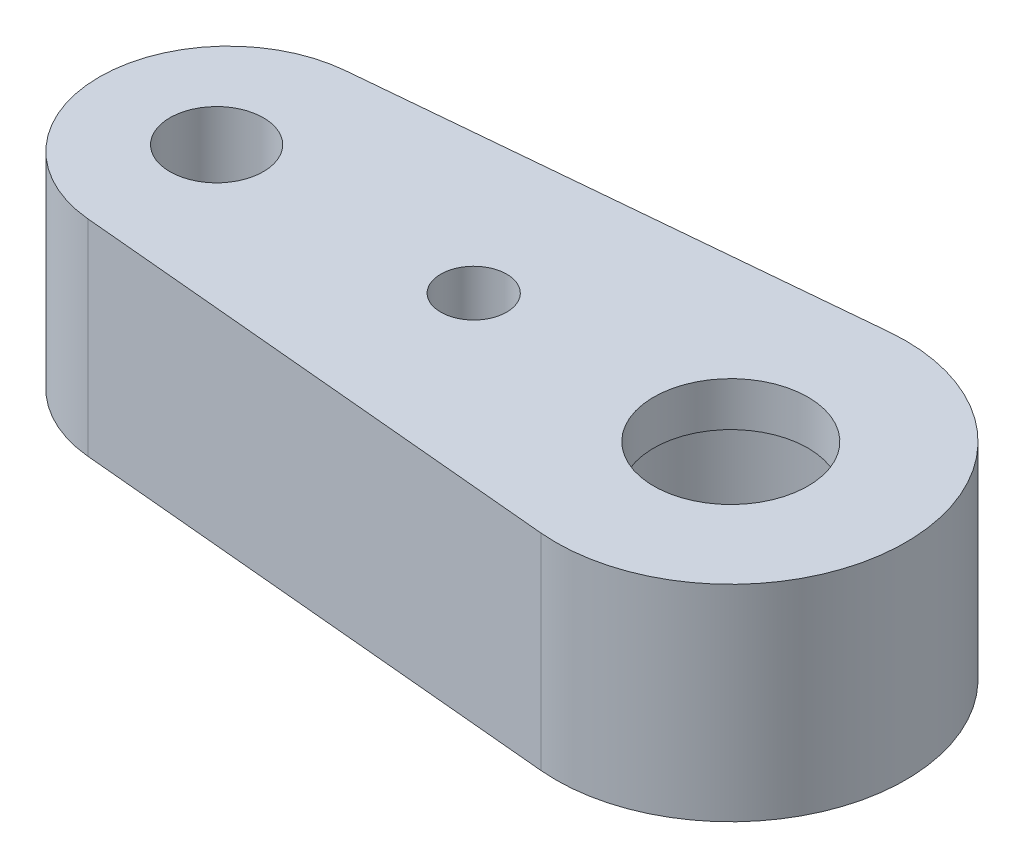
SolidWorks part; units mm, degrees
ref_plane "Front Plane" through (0, 0, 0) normal (0, 0, 1) x (1, 0, 0)
ref_plane "Top Plane" through (0, 0, 0) normal (0, 1, 0) x (1, 0, 0)
ref_plane "Right Plane" through (0, 0, 0) normal (1, 0, 0) x (0, 0, -1)
sketch "Sketch1" plane through (0, 0, 0) normal (0, 1, 0) x (1, 0, 0)
  line L0 (-5, 1.25) -> (-0.1548, 1.6929)
  line L1 (-5, -1.25) -> (-0.1548, -1.6929)
  line L2 (-2.5, 0) -> (0, 0) construction
  line L3 (-2.5, 0) -> (-5, 0) construction
  line L4 (-5, 1.25) -> (-5, 0) construction
  line L5 (-5, 0) -> (-5, -1.25) construction
  arc A0 (-0.1548, -1.6929) -> (-0.1548, 1.6929) centre (0, 0) ccw
  arc A1 (-5, 1.25) -> (-5, -1.25) centre (-4.8857, 0) ccw
  dimension "D1" = 2.5
  dimension "D2" = 3.4
  dimension "D3" = 2.5
  dimension "D4" = 1.25
extrude "Boss-Extrude1" add sketch "Sketch1" along normal blind 1 and the other way blind 1
sketch "Sketch4" plane through (0, 0, 0) normal (0, 0, 1) x (1, 0, 0)
  line L0 (1.145, 0) -> (1.145, 0.465)
  line L1 (1.145, 0.465) -> (0.75, 0.5708)
  line L2 (0.75, 0.5708) -> (0.75, 1)
  line L3 (1.7, 1) -> (-0.1548, 1) construction
  line L4 (0, 0) -> (1.145, 0) construction
  line L5 (1.145, 0) -> (1.145, -0.465)
  line L6 (1.145, -0.465) -> (0.75, -0.5708)
  line L7 (-0.1548, -1) -> (1.7, -1) construction
  line L9 (0, -1) -> (0, 1)
  line L10 (0, 1) -> (0.75, 1)
  line L11 (0.75, -0.5708) -> (0.75, -1)
  line L12 (0, -1) -> (0.75, -1)
  dimension "D1" = 0.465
  dimension "D2" = 105
  dimension "D3" = 1.145
  dimension "D4" = 0.75
revolve "Cut-Revolve1" cut sketch "Sketch4" angle 360 about L9
sketch "Sketch5" plane through (0, 1, 0) normal (0, 1, 0) x (1, 0, 0)
  circle A0 centre (-2.5, 0) radius 0.3207
  circle A1 centre (-5, 0) radius 0.4547
  dimension "D1" = 0.6414
  dimension "D2" = 0.9093
extrude "Cut-Extrude1" cut sketch "Sketch5" against normal up to next
